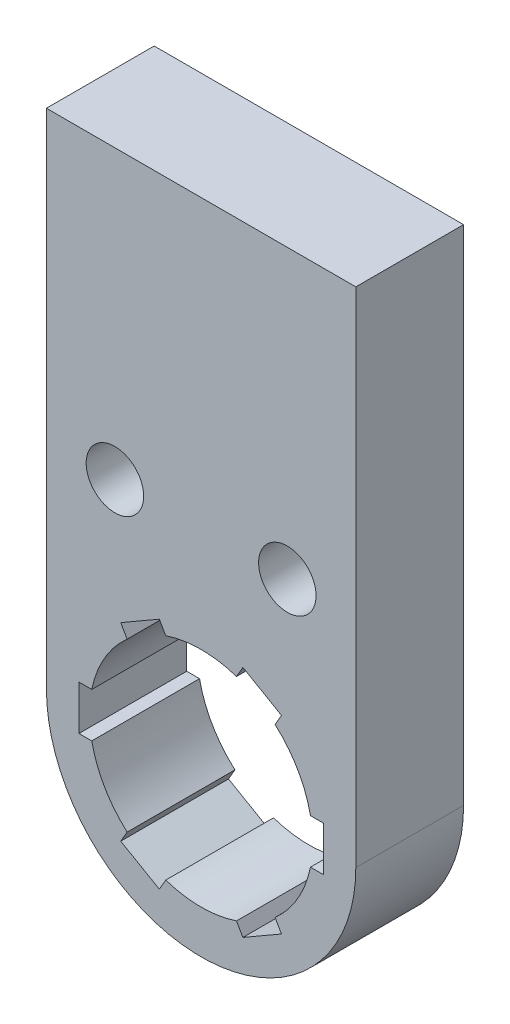
SolidWorks part; units mm, degrees
ref_plane "Front" through (0, 0, 0) normal (0, 0, 1) x (1, 0, 0)
ref_plane "Top" through (0, 0, 0) normal (0, 1, 0) x (1, 0, 0)
ref_plane "Right" through (0, 0, 0) normal (1, 0, 0) x (0, 0, -1)
sketch "Sketch1" plane through (0, 0, 0) normal (0, 0, 1) x (1, 0, 0)
  line L0 (0, -4.125) -> (0, 4.125) construction
  line L1 (-10.765, 17.5) -> (10.765, 17.5)
  line L2 (-10.765, 17.5) -> (-10.765, -17.5)
  line L4 (10.765, 17.5) -> (10.765, -17.5)
  line L5 (-10.765, 17.5) -> (10.765, -17.5) construction
  line L6 (-10.765, -17.5) -> (10.765, 17.5) construction
  line L7 (4.125, 0) -> (-4.125, 0) construction
  line L9 (0, -12.5) -> (0, 17.5) construction
  line L10 (-10.765, 0) -> (10.765, 0) construction
  arc A0 (-10.765, -17.5) -> (10.765, -17.5) centre (0, -17.5) ccw
  circle A1 centre (0, -17.5) radius 4.765
  circle A2 centre (-6, -2.5) radius 2
  circle A4 centre (6, -2.5) radius 2
  point P0 (0, 0)
  point P17 (0, 0)
  dimension "D3" = 9.53
  dimension "D4" = 4
  dimension "D5" = 6
  dimension "D1" = 21.53
  dimension "D2" = 35
  dimension "D6" = 20
extrude "Boss-Extrude1" add sketch "Sketch1" along normal blind 7.5
sketch "Sketch3" plane through (0, 0, 7.5) normal (0, 0, 1) x (1, 0, 0)
  line L0 (-5.5923, -10.9138) -> (-2.9077, -9.3638)
  line L1 (-8.5, -19.05) -> (8.5, -19.05)
  line L2 (-8.5, -19.05) -> (-8.5, -15.95)
  line L3 (-8.5, -15.95) -> (8.5, -15.95)
  line L4 (8.5, -19.05) -> (8.5, -15.95)
  line L5 (-8.5, -19.05) -> (8.5, -15.95) construction
  line L6 (-8.5, -15.95) -> (8.5, -19.05) construction
  line L11 (-5.5923, -10.9138) -> (2.9077, -25.6362)
  line L12 (2.9077, -25.6362) -> (5.5923, -24.0862)
  line L13 (-2.9077, -9.3638) -> (5.5923, -24.0862)
  line L14 (2.9077, -9.3638) -> (5.5923, -10.9138)
  line L15 (2.9077, -9.3638) -> (-5.5923, -24.0862)
  line L16 (-5.5923, -24.0862) -> (-2.9077, -25.6362)
  line L17 (5.5923, -10.9138) -> (-2.9077, -25.6362)
  line L18 (8.5, -15.95) -> (8.5, -19.05)
  line L19 (8.5, -15.95) -> (-8.5, -15.95)
  line L20 (-8.5, -15.95) -> (-8.5, -19.05)
  line L21 (8.5, -19.05) -> (-8.5, -19.05)
  circle A0 centre (0, -17.5) radius 4.765 construction
  circle A2 centre (0, -17.5) radius 7.765
  dimension "D3" = 3
  dimension "D1" = 4
  dimension "D2" = 17
  dimension "D4" = 3.1
extrude "Cut-Extrude1" cut sketch "Sketch3" against normal up to next contours A2 L13 L0 L11 | A2 L3 L2 L1 | A2 L15 L16 L17 | A2 L11 L12 L13 | A2 L21 L4 L19 | A2 L17 L14 L15 | A2 region at (-4.0526, -10.4807, 7.5) region at (-8.1052, -17.5, 7.5) region at (4.0526, -10.4807, 7.5) region at (-4.0526, -24.5193, 7.5) region at (8.1052, -17.5, 7.5) region at (4.0526, -24.5193, 7.5)
